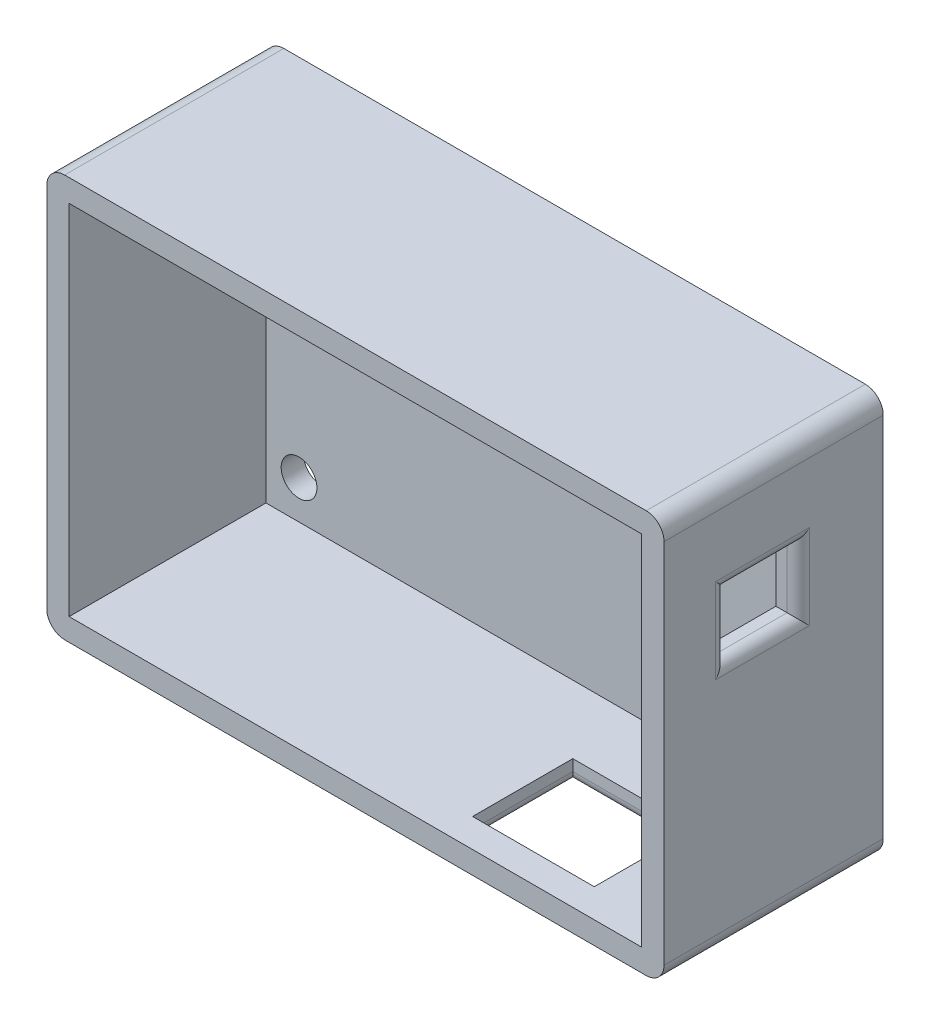
SolidWorks part; units mm, degrees
ref_plane "Front Plane" through (0, 0, 0) normal (0, 0, 1) x (1, 0, 0)
ref_plane "Top Plane" through (0, 0, 0) normal (0, 1, 0) x (1, 0, 0)
ref_plane "Right Plane" through (0, 0, 0) normal (1, 0, 0) x (0, 0, -1)
sketch "Sketch1" plane through (0, 0, 0) normal (0, 0, 1) x (1, 0, 0)
  line L1 (-43.815, -28.575) -> (43.815, -28.575)
  line L2 (-43.815, -28.575) -> (-43.815, 28.575)
  line L3 (-43.815, 28.575) -> (43.815, 28.575)
  line L4 (43.815, -28.575) -> (43.815, 28.575)
  line L5 (-43.815, -28.575) -> (43.815, 28.575) construction
  line L6 (-43.815, 28.575) -> (43.815, -28.575) construction
  point P0 (0, 0)
  dimension "D1" = 87.63
  dimension "D2" = 57.15
extrude "Boss-Extrude1" add sketch "Sketch1" along normal blind 31.115
sketch "Sketch2" plane through (0, 0, 31.115) normal (0, 0, 1) x (1, 0, 0)
  line L0 (-43.815, 28.575) -> (-43.815, -28.575) construction
  line L1 (40.64, -25.4) -> (-40.64, -25.4)
  line L2 (40.64, -25.4) -> (40.64, 25.4)
  line L3 (40.64, 25.4) -> (-40.64, 25.4)
  line L4 (-40.64, -25.4) -> (-40.64, 25.4)
  line L5 (40.64, -25.4) -> (-40.64, 25.4) construction
  line L6 (40.64, 25.4) -> (-40.64, -25.4) construction
  line L7 (43.815, 28.575) -> (-43.815, 28.575) construction
  point P0 (0, 0)
  dimension "D1" = 3.175
  dimension "D2" = 3.175
extrude "Cut-Extrude1" cut sketch "Sketch2" against normal blind 27.94
sketch "Sketch3" plane through (0, 0, 3.175) normal (0, 0, 1) x (1, 0, 0)
  line L0 (-40.64, 0) -> (40.64, 0) construction
  line L2 (-40.64, 25.4) -> (-40.64, -25.4) construction
  line L3 (40.64, -25.4) -> (40.64, 25.4) construction
  line L4 (0, 25.4) -> (0, -25.4) construction
  line L5 (40.64, 25.4) -> (-40.64, 25.4) construction
  line L6 (-40.64, -25.4) -> (40.64, -25.4) construction
  circle A0 centre (-35.941, 19.939) radius 2.54
  circle A1 centre (-35.941, -19.939) radius 2.54
  circle A2 centre (35.941, -19.939) radius 2.54
  circle A3 centre (35.941, 19.939) radius 2.54
  dimension "D1" = 19.939
  dimension "D2" = 35.941
  dimension "D3" = 5.08
extrude "Cut-Extrude2" cut sketch "Sketch3" against normal through all
fillet "Fillet2" radius 2.54 4 edges at (43.815, -28.575, 15.5575) (43.815, 28.575, 15.5575) (-43.815, -28.575, 15.5575) (-43.815, 28.575, 15.5575)
sketch "Sketch4" plane through (43.815, 0, 0) normal (1, 0, 0) x (0, 0, -1)
  line L1 (-22.225, 15.875) -> (-12.065, 15.875)
  line L2 (-22.225, 15.875) -> (-22.225, 6.985)
  line L3 (-22.225, 6.985) -> (-12.065, 6.985)
  line L4 (-12.065, 15.875) -> (-12.065, 6.985)
  line L5 (-31.115, 28.575) -> (0, 28.575) construction
  line L6 (-31.115, -26.035) -> (-31.115, 26.035) construction
  dimension "D1" = 10.16
  dimension "D2" = 8.89
  dimension "D3" = 12.7
  dimension "D4" = 8.89
extrude "Cut-Extrude3" cut sketch "Sketch4" against normal up to next
sketch "Sketch5" plane through (0, -28.575, 0) normal (0, -1, 0) x (1, 0, 0)
  line L0 (41.275, 0) -> (41.275, 31.115) construction
  line L1 (12.573, 27.051) -> (29.845, 27.051)
  line L2 (12.573, 27.051) -> (12.573, 12.827)
  line L3 (12.573, 12.827) -> (29.845, 12.827)
  line L4 (29.845, 27.051) -> (29.845, 12.827)
  line L5 (-41.275, 31.115) -> (41.275, 31.115) construction
  dimension "D1" = 11.43
  dimension "D2" = 4.064
  dimension "D3" = 14.224
  dimension "D4" = 17.272
extrude "Cut-Extrude4" cut sketch "Sketch5" against normal up to next
fillet "Fillet4" radius 1.5875 4 edges at (21.209, -28.575, 12.827) (29.845, -28.575, 19.939) (21.209, -28.575, 27.051) (12.573, -28.575, 19.939)
fillet "Fillet5" radius 1.5875 4 edges at (43.815, 11.43, 12.065) (43.815, 15.875, 17.145) (43.815, 11.43, 22.225) (43.815, 6.985, 17.145)
